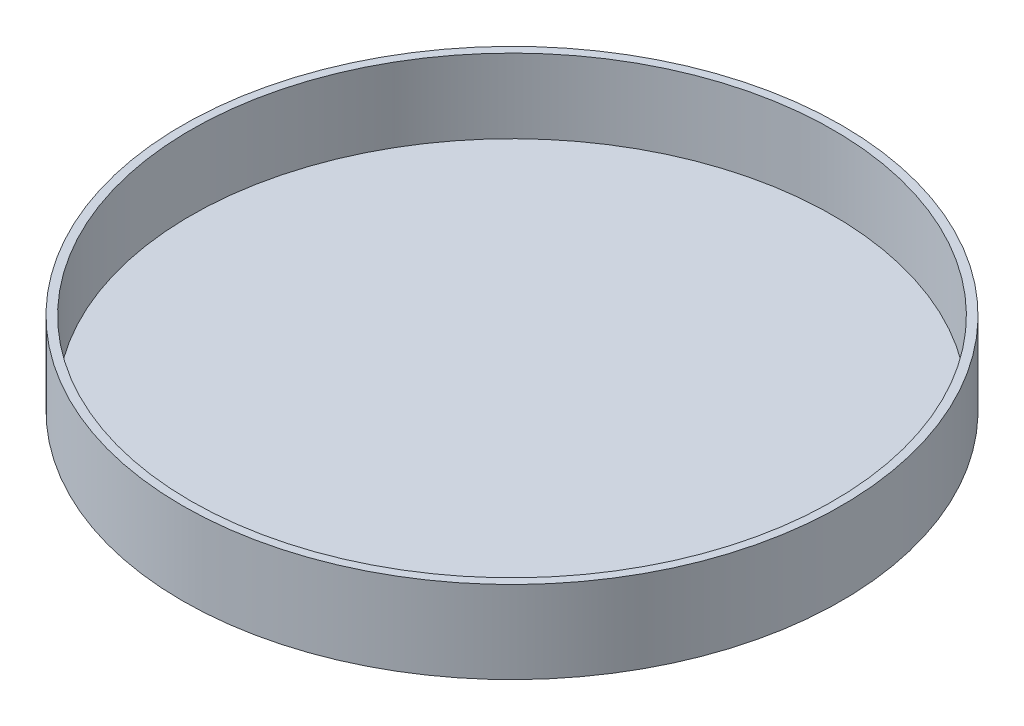
SolidWorks part; units mm, degrees
ref_plane "Plan de face" through (0, 0, 0) normal (0, 0, 1) x (1, 0, 0)
ref_plane "Plan de dessus" through (0, 0, 0) normal (0, 1, 0) x (1, 0, 0)
ref_plane "Plan de droite" through (0, 0, 0) normal (1, 0, 0) x (0, 0, -1)
sketch "Esquisse1" plane through (0, 0, 0) normal (0, 1, 0) x (1, 0, 0)
  circle A0 centre (0, 0) radius 160
  dimension "D1" = 320
extrude "Boss.-Extru.1" add sketch "Esquisse1" along normal blind 40
sketch "Esquisse2" plane through (0, 40, 0) normal (0, 1, 0) x (1, 0, 0)
  circle A0 centre (0, 0) radius 156
  circle A3 centre (0, 0) radius 160 construction
  dimension "D2" = 4
extrude "Enlèv. mat.-Extru.1" cut sketch "Esquisse2" against normal blind 4
shell "Coque2" thickness 4 removed face at (0, 36, 156)
